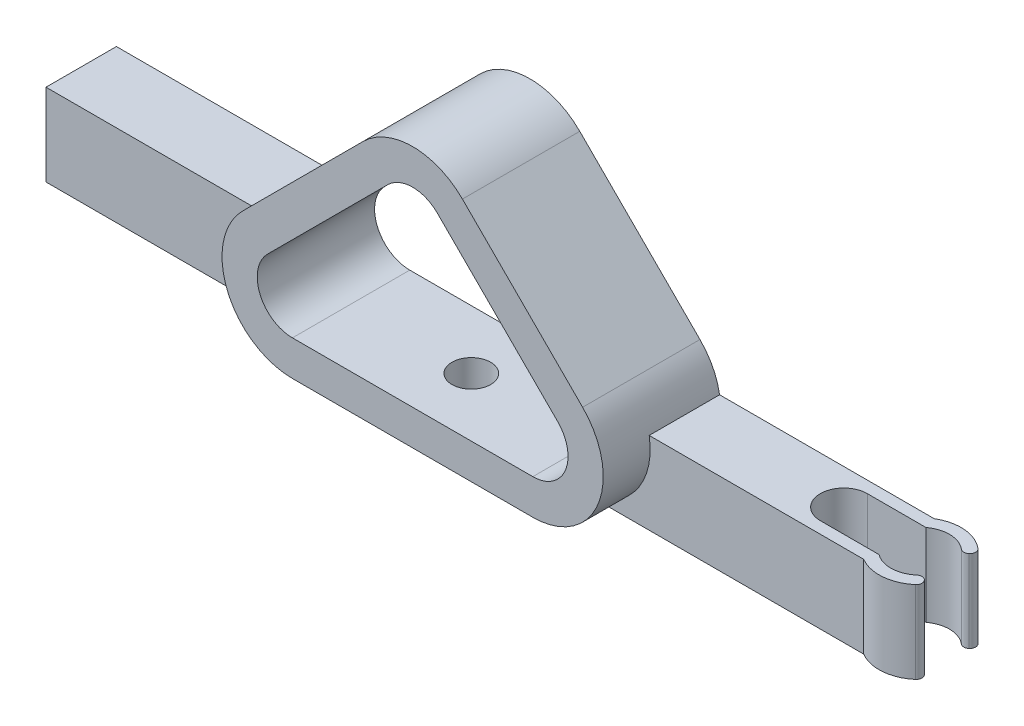
SolidWorks part; units mm, degrees
material "PS HI"
ref_plane "Face" through (0, 0, 0) normal (0, 0, 1) x (1, 0, 0)
ref_plane "Dessus" through (0, 0, 0) normal (0, 1, 0) x (1, 0, 0)
ref_plane "Droite" through (0, 0, 0) normal (1, 0, 0) x (0, 0, -1)
sketch "Esquisse5" plane through (0, 0, 0) normal (0, 0, 1) x (1, 0, 0)
  line L0 (0, 0) -> (0, 24.0675) construction
  line L1 (0, -6) -> (39.0742, -6) construction
  line L2 (10.2426, -9) -> (-10.2426, -9)
  line L3 (-12.364, -3.8787) -> (-2.1213, 6.364)
  line L4 (12.364, -3.8787) -> (2.1213, 6.364)
  line L5 (-14.4853, -1.7574) -> (-4.2426, 8.4853)
  line L6 (14.4853, -1.7574) -> (4.2426, 8.4853)
  line L7 (10.2426, -12) -> (-10.2426, -12)
  line L8 (-24.7279, -12) -> (0, 12.7279) construction
  line L9 (24.7279, -12) -> (0, 12.7279) construction
  line L10 (24.7279, -12) -> (-24.7279, -12) construction
  line L11 (-17.4853, -9) -> (0, 8.4853) construction
  line L12 (17.4853, -9) -> (0, 8.4853) construction
  line L13 (17.4853, -9) -> (-17.4853, -9) construction
  circle A0 centre (0, 0) radius 6 construction
  arc A1 (-4.2426, 8.4853) -> (4.2426, 8.4853) centre (0, 4.2426) cw
  arc A2 (14.4853, -1.7574) -> (10.2426, -12) centre (10.2426, -6) cw
  arc A3 (-14.4853, -1.7574) -> (-10.2426, -12) centre (-10.2426, -6) ccw
  arc A4 (-2.1213, 6.364) -> (2.1213, 6.364) centre (0, 4.2426) cw
  arc A5 (12.364, -3.8787) -> (10.2426, -9) centre (10.2426, -6) cw
  arc A6 (-10.2426, -9) -> (-12.364, -3.8787) centre (-10.2426, -6) cw
  point P11 (0, -9)
  point P26 (0, 8.4853)
  dimension "D1" = 12
  dimension "D2" = 3
  dimension "D5" = 6
  dimension "D6" = 6
  dimension "D7" = 6
  dimension "D8" = 3
  dimension "D9" = 3
  dimension "D3" = 3
  dimension "D10" = 90
  dimension "D4" = 3
extrude "Boss.-Extru.4" add sketch "Esquisse5" along normal blind 10
ref_point "Point1"
ref_axis "Axe1" through (0, -12, 5) along (0, -1, 0)
sketch "Esquisse6" plane through (0, -12, 0) normal (0, -1, 0) x (1, 0, 0)
  line L0 (-10.2426, 10) -> (10.2426, 10) construction
  line L3 (10.2426, 10) -> (10.2426, 0) construction
  circle A0 centre (0, 5) radius 4
  circle A1 centre (0, 5) radius 2
  dimension "D1" = 8
  dimension "D2" = 5
  dimension "D3" = 10.2426
  dimension "D4" = 4
hole_wizard "Trou taraudé M43" positions "Esquisse3D4" profile "Esquisse12" tap size "M4" standard "ISO" end condition up to next
sketch3d "Esquisse3D4"
  point P0 (0, -12, 5)
  point P4 (0, -12, 5)
cosmetic thread "Filetage de perçage4" parameters "D2"=4
cosmetic thread "Filetage de perçage5" parameters "D2"=4
sketch "Esquisse12" plane through (0, -12, 5) normal (1, 0, 0) x (0, 0, -1)
  line L0 (0, 0) -> (0, 22.2426)
  line L1 (0, 22.2426) -> (1.65, 22.2426)
  line L2 (1.65, 22.2426) -> (1.65, 0)
  line L5 (1.65, 0) -> (0, 0)
  line L11 (0, -6.35) -> (0, 107.95) construction
  dimension "Diamètre du trou pour taraudage jusqu'au prochain" = 3.3
  dimension "Profondeur du trou pour taraudage jusqu'au prochain" = 22.2426
sketch "Esquisse13" plane through (0, 0, 0) normal (0, 0, 1) x (1, 0, 0)
  line L0 (-10.2426, -12) -> (-35.2426, -12)
  line L1 (-35.2426, -12) -> (-35.2426, -5)
  line L2 (-35.2426, -5) -> (-16.1587, -5)
  line L3 (10.2426, -12) -> (30.2426, -12)
  line L4 (30.2426, -12) -> (30.2426, -5)
  line L5 (30.2426, -5) -> (16.1587, -5)
  arc A0 (-14.4853, -1.7574) -> (-10.2426, -12) centre (-10.2426, -6) ccw construction
  arc A2 (10.2426, -12) -> (14.4853, -1.7574) centre (10.2426, -6) ccw construction
  arc A3 (-10.2426, -12) -> (-16.1587, -5) centre (-10.2426, -6) cw
  arc A4 (10.2426, -12) -> (16.1587, -5) centre (10.2426, -6) ccw
  dimension "D1" = 7
  dimension "D2" = 25
  dimension "D3" = 20
  dimension "D4" = 7
extrude "Boss.-Extru.5" add sketch "Esquisse13" along normal blind 6
ref_plane "Plan1" through (0, -12, 0) normal (0, -1, 0) x (-1, 0, 0)
sketch "Esquisse16" plane through (0, -12, 0) normal (0, -1, 0) x (-1, 0, 0)
  line L3 (-30.2426, 0) -> (-30.2426, -6)
sketch "Esquisse18" plane through (0, -12, 0) normal (0, -1, 0) x (-1, 0, 0)
  line L0 (-30.2426, 0) -> (-34.4399, 0)
  line L1 (-36.1854, -3) -> (7.299, -3) construction
  line L2 (-30.2426, -6) -> (-34.4399, -6)
  line L3 (-34.4399, 0) -> (-34.4399, -6)
  line L4 (-30.2426, 0) -> (-30.2426, -6)
  line L5 (-38.9238, -5.2498) -> (-38.1578, -4.607)
  line L6 (-38.9238, -0.7502) -> (-38.1578, -1.393)
  line L7 (-36.2426, -3) -> (-41.1335, 1.1039)
  line L8 (-36.2426, -3) -> (-41.1335, -7.1039)
  arc A1 (-34.4399, 0) -> (-38.9238, -0.7502) centre (-36.2426, -3) ccw
  arc A2 (-38.1578, -4.607) -> (-38.1578, -1.393) centre (-36.2426, -3) ccw
  arc A5 (-34.4399, -6) -> (-38.9238, -5.2498) centre (-36.2426, -3) cw
  arc A6 (-38.139, -1.4088) -> (-38.1578, -1.393) centre (-38.4801, -1.7963) ccw
  dimension "D2" = 40
  dimension "D3" = 1
  dimension "D4" = 2.5
  dimension "D5" = 6
  dimension "D1" = 3
extrude "Boss.-Extru.8" add sketch "Esquisse18" against normal blind 7 contours A2 L1 L4 L0 L3 | L1 A2 L3 L2 L4 | A1 A2 L3 | A5 L3 A2 region at (32.213, -12, 1.4409) region at (36.5562, -12, 0.287) region at (32.213, -12, 4.5591) region at (36.5562, -12, 5.713)
fillet "Congé1" radius 0.5 4 edges at (38.1578, -8.5, 1.393) (38.9238, -8.5, 0.7502) (38.9238, -8.5, 5.2498) (38.1578, -8.5, 4.607)
sketch "Esquisse19" plane through (0, -12, 0) normal (0, -1, 0) x (1, 0, 0)
  line L0 (33.7426, 3) -> (27.7865, 3) construction
  line L1 (29.7426, 1) -> (34.7426, 1)
  line L2 (29.7426, 5) -> (34.7426, 5)
  arc A0 (37.8631, 4.9037) -> (37.8631, 1.0963) centre (36.2426, 3) ccw construction
  arc A1 (29.7426, 5) -> (29.7426, 1) centre (29.7426, 3) ccw
  arc A2 (34.7426, 5) -> (34.7426, 1) centre (36.2426, 3) ccw
  dimension "D1" = 4
  dimension "D2" = 4
extrude "Enlèv. mat.-Extru.1" cut sketch "Esquisse19" against normal through all
